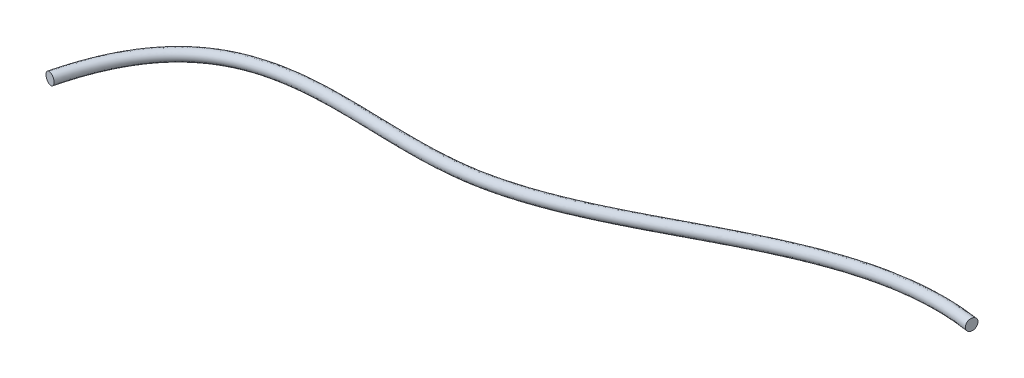
SolidWorks part; units mm, degrees
ref_plane "Front Plane" through (0, 0, 0) normal (0, 0, 1) x (1, 0, 0)
ref_plane "Top Plane" through (0, 0, 0) normal (0, 1, 0) x (1, 0, 0)
ref_plane "Right Plane" through (0, 0, 0) normal (1, 0, 0) x (0, 0, -1)
sketch "Sketch1" plane through (0, 0, 0) normal (0, 1, 0) x (1, 0, 0)
  spline S0 degree 3 poles (-173.971, -13.2282) (-158.837, 47.7098) (-53.1948, 0.788) (15.5437, 83.5201) (68.1453, 75.7616) knots 0 0 0 0 0.458344 1 1 1 1
sweep "Sweep1" add path "Sketch1" circular profile diameter 4 parameters "D3"=4
